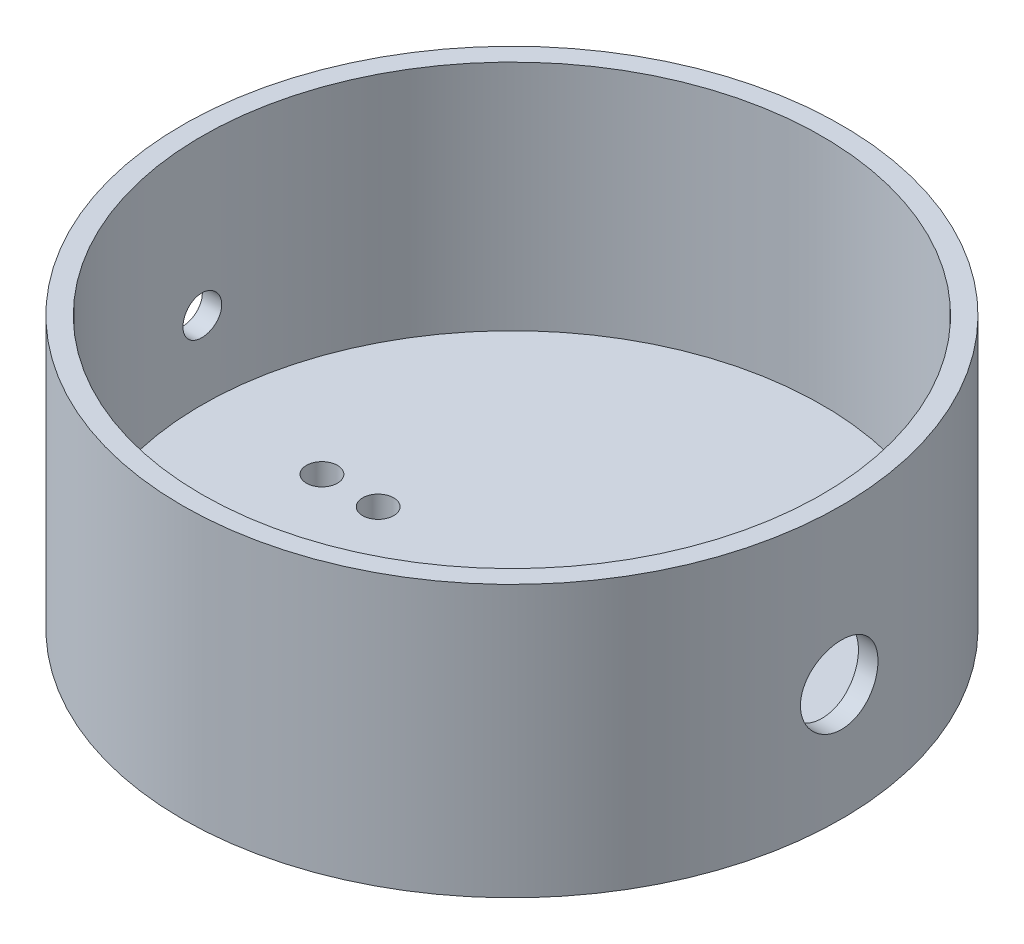
SolidWorks part; units mm, degrees
ref_plane "Front Plane" through (0, 0, 0) normal (0, 0, 1) x (1, 0, 0)
ref_plane "Top Plane" through (0, 0, 0) normal (0, 1, 0) x (1, 0, 0)
ref_plane "Right Plane" through (0, 0, 0) normal (1, 0, 0) x (0, 0, -1)
sketch "Sketch1" plane through (0, 0, 0) normal (0, 1, 0) x (1, 0, 0)
  circle A0 centre (0, 0) radius 42.5
  point P3 (0, 0)
  dimension "D1" = 85
extrude "Boss-Extrude1" add sketch "Sketch1" along normal blind 5
sketch "Sketch2" plane through (0, 5, 0) normal (0, 1, 0) x (1, 0, 0)
  circle A0 centre (0, 0) radius 40
  circle M1 centre (0, 0) radius 42.5
  dimension "D1" = 80
extrude "Boss-Extrude2" add sketch "Sketch2" along normal blind 30 contours A0 M1 region at (-41.2979, 5, 0)
sketch "Sketch3" plane through (0, 0, 0) normal (0, -1, 0) x (1, 0, 0)
  circle A3 centre (0, 0) radius 42.5
  arc A6 (-7.8151, -9.7199) -> (-25.9581, -15.5245) centre (-17.8151, -9.7199) cw
  circle A7 centre (-24.5, 0) radius 2
  circle A8 centre (-17.25, 0) radius 2
  arc A9 (-7.8151, -9.7199) -> (-7.4106, 9.9848) centre (-1.1616, 0) cw
  arc A10 (-26.6881, 13.3259) -> (-7.4106, 9.9848) centre (-17.4036, 9.6111) cw
  spline S3 degree 2 poles (-29, -6.35) (-28.6991, -11.6005) (-25.178, -16.4866) knots 0.672683 0.672683 0.672683 1 1 1
  spline S4 degree 2 poles (-29, 6.35) (-30.0423, 0) (-29, -6.35) knots 0 0 0 1 1 1
  spline S5 degree 3 poles (-25.9558, 14.7939) (-27.3295, 12.1453) (-28.5409, 9.3136) (-29, 6.35) knots 0 0 0 0 0.277553 0.277553 0.277553 0.277553
  point P0 (0, 0)
  point P6 (0, 0)
  point P13 (0, -0.1316)
  dimension "D2" = 12.7
extrude "Boss-Extrude3" add sketch "Sketch3" along normal blind 5 contours A10 S5 S4 S3 A6 A9 A8 A7 region at (-14.3478, 0, -18.617)
extrude "Cut-Extrude1" cut sketch "Sketch3<3>" against normal through all both and the other way through all contours A8 | A7 region at (-24.5, 0, 0) region at (-17.25, 0, 0)
sketch "Sketch3<3>" plane through (0, 0, 0) normal (0, -1, 0) x (1, 0, 0) same geometry as "Sketch3"
sketch "Sketch4" plane through (0, 0, 0) normal (1, 0, 0) x (0, 0, -1)
  circle A0 centre (0, 15) radius 2.5
  circle A1 centre (0, 15) radius 5
  point P4 (0, 0)
  point P5 (0, 0)
  dimension "D2" = 5
  dimension "D3" = 10
  dimension "D1" = 15
extrude "Cut-Extrude4" cut sketch "Sketch4" against normal up to surface (42.4264 mm away) contours A0 up to face at (0, 0, 42.5)
extrude "Cut-Extrude8" cut sketch "Sketch4<5>" along normal blind 50 contours A0 | A1 A0 region at (0, 15, 0) region at (0, 15, 4.8586)
sketch "Sketch4<5>" plane through (0, 0, 0) normal (1, 0, 0) x (0, 0, -1) same geometry as "Sketch4"
